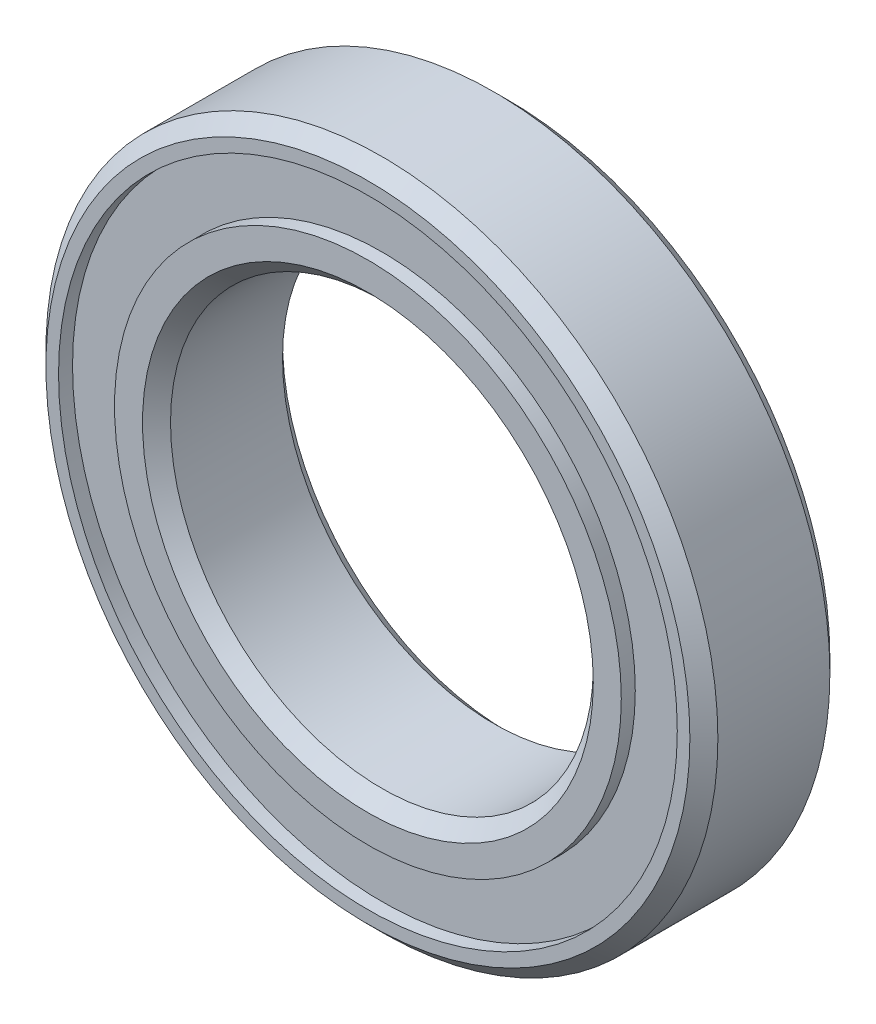
SolidWorks part; units mm, degrees
material "Gerais  - 6061-T6"
ref_plane "Plano frontal" through (0, 0, 0) normal (0, 0, 1) x (1, 0, 0)
ref_plane "Plano superior" through (0, 0, 0) normal (0, 1, 0) x (1, 0, 0)
ref_plane "Plano direito" through (0, 0, 0) normal (1, 0, 0) x (0, 0, -1)
sketch "Esboço1" plane through (0, 0, 0) normal (0, 0, 1) x (1, 0, 0)
  circle A0 centre (0, 0) radius 12
  circle A1 centre (0, 0) radius 7.55
  dimension "D1" = 24
  dimension "D2" = 15.1
extrude "Ressalto-extrusão1" add sketch "Esboço1" along normal blind 5
sketch "Esboço2" plane through (0, 0, 5) normal (0, 0, 1) x (1, 0, 0)
  circle A0 centre (0, 0) radius 11.05
  circle A1 centre (0, 0) radius 9.05
  circle A2 centre (0, 0) radius 7.55 construction
  circle A3 centre (0, 0) radius 12 construction
  point P4 (0, 7.55)
  point P5 (0, 9.05)
  point P8 (0, 12)
  point P9 (0, 11.05)
  dimension "D1" = 1.5
  dimension "D2" = 2
extrude "Corte-extrusão1" cut sketch "Esboço2" against normal blind 0.5
sketch "Esboço3" plane through (0, 0, 0) normal (0, 0, -1) x (-1, 0, 0)
  circle A0 centre (0, 0) radius 9.05 construction
  circle A1 centre (0, 0) radius 11.05 construction
  circle A2 centre (0, 0) radius 9.05
  circle A3 centre (0, 0) radius 11.05
extrude "Corte-extrusão2" cut sketch "Esboço3" against normal blind 0.5
chamfer "Chanfro1" distance 0.5 angle 45 4 edges at (12, 0, 5) (12, 0, 0) (7.55, 0, 0) (7.55, 0, 5)
